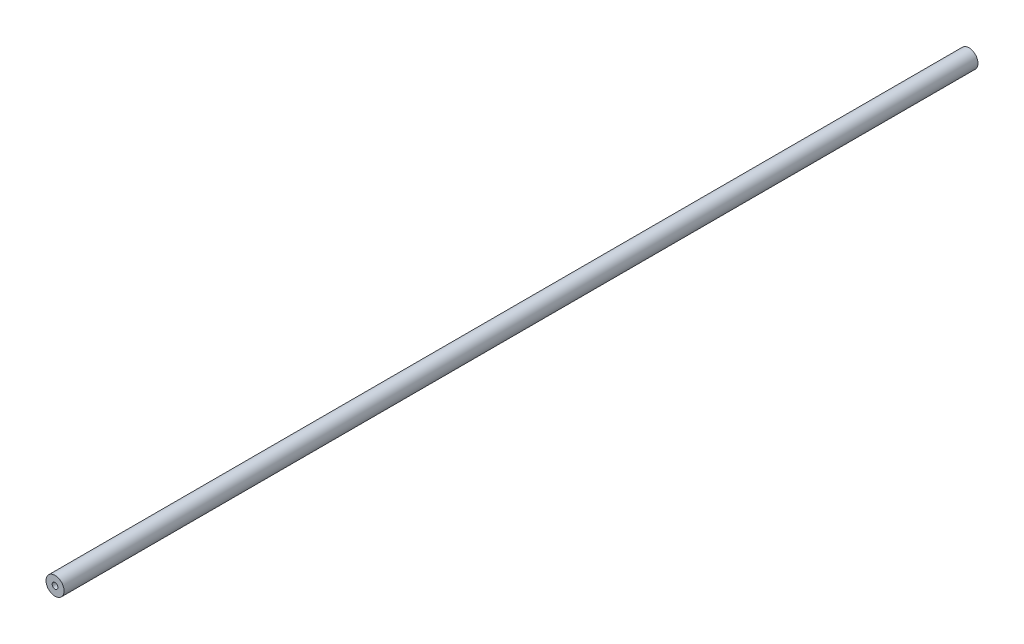
SolidWorks part; units mm, degrees
material "6061-T6 (SS)"
ref_plane "Front Plane" through (0, 0, 0) normal (0, 0, 1) x (1, 0, 0)
ref_plane "Top Plane" through (0, 0, 0) normal (0, 1, 0) x (1, 0, 0)
ref_plane "Right Plane" through (0, 0, 0) normal (1, 0, 0) x (0, 0, -1)
sketch "Sketch1" plane through (0, 0, 0) normal (0, 0, 1) x (1, 0, 0)
  circle A0 centre (0, 0) radius 6.35
  dimension "D1" = 12.7
extrude "Boss-Extrude1" add sketch "Sketch1" along normal blind 641.858
hole_wizard "#10-32 Tapped Hole1" positions "Sketch3" profile "Sketch2" tap size "#10-32" standard "ANSI Inch"
sketch "Sketch3" plane through (0, 0, 641.858) normal (0, 0, 1) x (1, 0, 0)
  point P0 (0, 0)
sketch "Sketch2" plane through (0, 0, 641.858) normal (1, 0, 0) x (0, -1, 0)
  line L0 (0, 0) -> (0, 14.9293)
  line L1 (0, 14.9293) -> (2.0193, 13.716)
  line L2 (2.0193, 13.716) -> (2.0193, 0)
  line L5 (2.0193, 0) -> (0, 0)
  line L10 (0, 14.9293) -> (-2.0193, 13.716) construction
  line L11 (0, -6.35) -> (0, 107.95) construction
  dimension "Tap Drill Dia." = 4.0386
  dimension "Tap Drill Depth" = 13.716
  dimension "Drill Angle" = 118
cosmetic thread "Hole Thread1"
hole_wizard "#10-32 Tapped Hole2" positions "Sketch5" profile "Sketch4" tap size "#10-32" standard "ANSI Inch"
sketch "Sketch5" plane through (0, 0, 0) normal (0, 0, -1) x (-1, 0, 0)
  point P0 (0, 0)
sketch "Sketch4" plane through (0, 0, 0) normal (1, 0, 0) x (0, 1, 0)
  line L0 (0, 0) -> (0, 14.9293)
  line L1 (0, 14.9293) -> (2.0193, 13.716)
  line L2 (2.0193, 13.716) -> (2.0193, 0)
  line L5 (2.0193, 0) -> (0, 0)
  line L10 (0, 14.9293) -> (-2.0193, 13.716) construction
  line L11 (0, -6.35) -> (0, 107.95) construction
  dimension "Tap Drill Dia." = 4.0386
  dimension "Tap Drill Depth" = 13.716
  dimension "Drill Angle" = 118
cosmetic thread "Hole Thread2"
